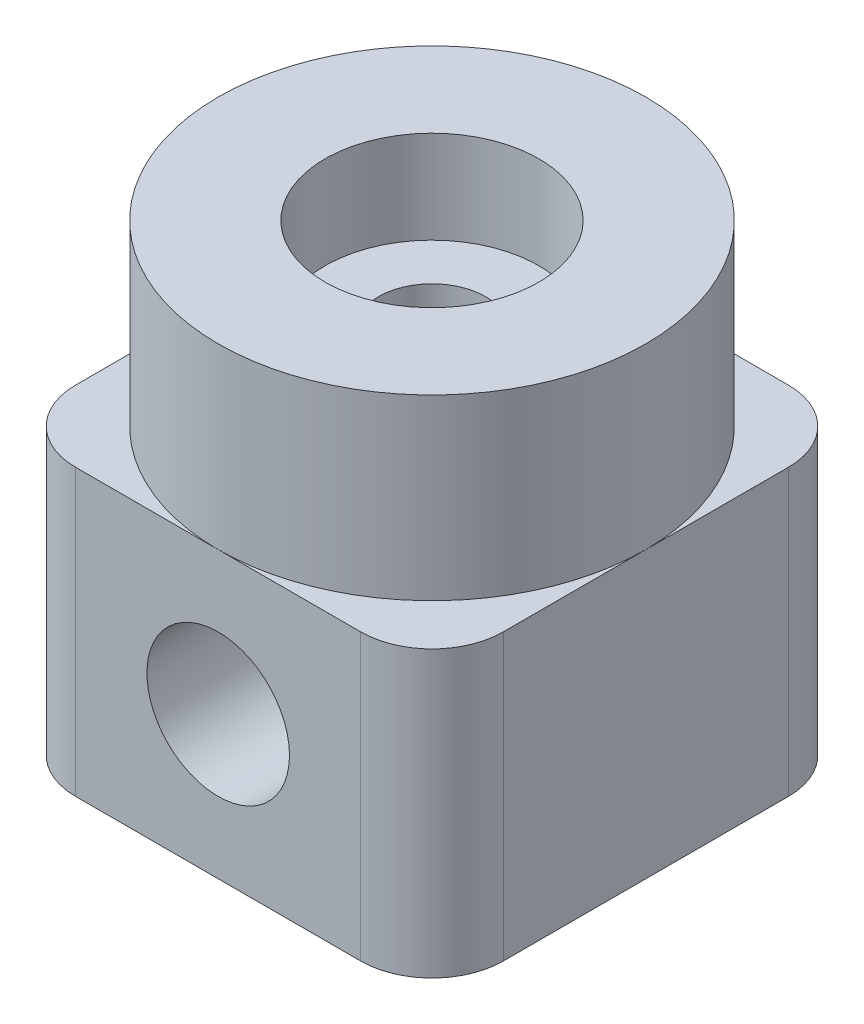
SolidWorks part; units mm, degrees
ref_plane "前视基准面" through (0, 0, 0) normal (0, 0, 1) x (1, 0, 0)
ref_plane "上视基准面" through (0, 0, 0) normal (0, 1, 0) x (1, 0, 0)
ref_plane "右视基准面" through (0, 0, 0) normal (1, 0, 0) x (0, 0, -1)
other "Configuration Table"
sketch "草图1" plane through (0, 0, 0) normal (0, 1, 0) x (1, 0, 0)
  circle A0 centre (0, 0) radius 6
  dimension "D1" = 12
extrude "凸台-拉伸1" add sketch "草图1" along normal blind 5
sketch "草图2" plane through (0, 0, 0) normal (0, 0, 1) x (1, 0, 0)
  line L0 (-2.5332, 0) -> (0, 0) construction
  line L1 (6, 0) -> (-6, 0)
  line L2 (-6, 0) -> (-6, -8)
  line L3 (-6, -8) -> (6, -8)
  line L4 (6, -8) -> (6, 0)
  point P6 (0, 0)
  dimension "D1" = 12
  dimension "D2" = 8
extrude "凸台-拉伸2" add sketch "草图2" against normal blind 6
extrude "凸台-拉伸3" add sketch "草图2<2>" along normal blind 6
sketch "草图2<2>" plane through (0, 0, 0) normal (0, 0, 1) x (1, 0, 0) same geometry as "草图2"
sketch "草图3" plane through (0, 0, 6) normal (0, 0, 1) x (1, 0, 0)
  line L0 (6, 0) -> (0, 0) construction
  line L1 (-6, 0) -> (-6, -8) construction
  circle A0 centre (0, -4) radius 2
  dimension "D1" = 4
  dimension "D2" = 4
  dimension "D3" = 6
extrude "切除-拉伸1" cut sketch "草图3" against normal through all
sketch "草图4" plane through (0, 5, 0) normal (0, 1, 0) x (1, 0, 0)
  circle A0 centre (0, 0) radius 1.5
  dimension "D1" = 3
extrude "切除-拉伸2" cut sketch "草图4" against normal blind 5
fillet "圆角1" radius 2 4 edges at (-6, -4, -6) (6, -4, -6) (6, -4, 6) (-6, -4, 6)
sketch "草图5" plane through (0, 5, 0) normal (0, 1, 0) x (1, 0, 0)
  circle A0 centre (0, 0) radius 3
  dimension "D1" = 6
extrude "切除-拉伸4" cut sketch "草图5" against normal blind 2.6 contours A0
